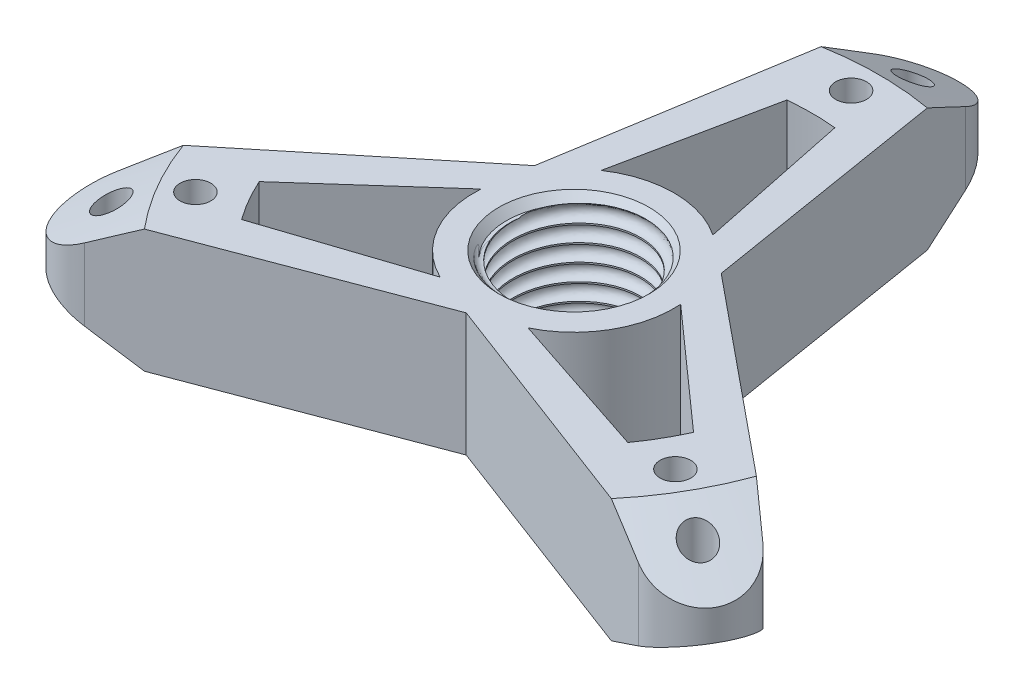
SolidWorks part; units mm, degrees
ref_plane "Front Plane" through (0, 0, 0) normal (0, 0, 1) x (1, 0, 0)
ref_plane "Top Plane" through (0, 0, 0) normal (0, 1, 0) x (1, 0, 0)
ref_plane "Right Plane" through (0, 0, 0) normal (1, 0, 0) x (0, 0, -1)
sketch "Sketch1" plane through (0, 0, 0) normal (0, 1, 0) x (1, 0, 0)
  line L26 (0, 0) -> (0, 22) construction
  line L27 (0, 0) -> (0, 22) construction
  line L36 (0, 0) -> (-6.0622, 3.5) construction
  line L37 (-2.9607, 22.4837) -> (-6.0622, 3.5)
  line L38 (-20.9518, -8.6778) -> (-6.0622, 3.5)
  line L39 (20.9518, -8.6778) -> (6.0622, 3.5)
  line L40 (2.9607, 22.4837) -> (6.0622, 3.5)
  line L41 (-17.9911, -13.8059) -> (0, -7)
  line L42 (17.9911, -13.8059) -> (0, -7)
  circle A24 centre (0, 22) radius 1
  circle A53 centre (19.0526, -11) radius 1
  circle A54 centre (-19.0526, -11) radius 1
  circle A61 centre (0, 0) radius 4.15
  circle A70 centre (0, 0) radius 22 construction
  arc A71 (-2.6648, 17.8017) -> (-17.2575, -5.1164) centre (0, 0) ccw construction
  arc A84 (2.9607, 22.4837) -> (-2.9607, 22.4837) centre (0, 22) ccw
  circle A85 centre (0, 0) radius 7 construction
  circle A86 centre (0, 0) radius 25 construction
  arc A87 (17.9911, -13.8059) -> (20.9518, -8.6778) centre (19.0526, -11) ccw
  arc A88 (-20.9518, -8.6778) -> (-17.9911, -13.8059) centre (-19.0526, -11) ccw
  circle A89 centre (0, 18) radius 1
  circle A90 centre (15.5885, -9) radius 1
  circle A91 centre (-15.5885, -9) radius 1
  point P21 (0, 0)
  point P31 (0, 0)
  point P33 (0, 0)
  point P37 (0, 0)
  point P47 (0, 0)
  point P48 (0, 0)
  point P66 (0, 0)
  dimension "D1" = 8.3
  dimension "D2" = 14
  dimension "D3" = 44
  dimension "D4" = 3
  dimension "D5" = 50
  dimension "D6" = 2
  dimension "D8" = 3
  dimension "D9" = 2
  dimension "D10" = 4
  dimension "D7" = 60
extrude "Boss-Extrude1" add sketch "Sketch1" against normal mid plane 8 contours A86 A24 A53 A54 A85 | A85 L40 A84 L37 A24 | L42 A87 L39 A85 A53 region at (0, 0, -24.4113)
ref_plane "Plane4" through (0, -5, 0) normal (0, 1, 0) x (1, 0, 0)
sketch "Sketch54" plane through (0, -5, 0) normal (0, 1, 0) x (1, 0, 0)
  circle A0 centre (0, 0) radius 4.15 construction
  circle A1 centre (0, 0) radius 4.15
curve "Helix/Spiral2" pitch 1.1 height 16.5 radius 4.15 left hand yes centre (0, -5, 0) axis (0, 1, 0) start towards (0, 0, 1)
sweep "Cut-Sweep4" cut path "Helix/Spiral2" align with end faces yes circular profile diameter 1 parameters "D3"=1
sketch "Sketch62" plane through (0, 4, 0) normal (0, 1, 0) x (1, 0, 0)
  circle A0 centre (0, 0) radius 4.8812
extrude "Cut-Extrude4" cut sketch "Sketch62" against normal blind 0.5 draft 45
mirror "Mirror6" about plane through (0, 0, 0) normal (0, 1, 0) of "Cut-Extrude4"
sketch "Sketch73" plane through (0, 0, 0) normal (1, 0, 0) x (0, 0, -1)
  line L0 (-14, -1) -> (-8.8038, -4)
  line L1 (-14, 4) -> (-14, -4) construction
  line L2 (-8.6778, -4) -> (3.5, -4) construction
  line L3 (-8.8038, -4) -> (-14, -8.8856)
  line L4 (-14, -8.8856) -> (-14, -1)
  line L5 (-14, -4) -> (-8.6778, -4) construction
  line L6 (0, 0) -> (0, -12.6592) construction
  dimension "D1" = 60
  dimension "D2" = 3
sketch "Sketch74" plane through (0, 0, 0) normal (1, 0, 0) x (0, 0, -1)
  line L0 (25, 1) -> (19.8038, 4)
  line L1 (25, -4) -> (25, 4) construction
  line L2 (22.4837, 4) -> (3.5, 4) construction
  line L3 (19.8038, 4) -> (25, 4)
  line L4 (25, 4) -> (22.4837, 4) construction
  line L5 (25, 4) -> (25, 1)
  dimension "D1" = 3
  dimension "D2" = 60
revolve "Cut-Revolve1" cut sketch "Sketch74" angle 360 about L6
mirror "Mirror8" about plane through (0, 0, 0) normal (0, 1, 0) of "Cut-Revolve1"
sketch "Sketch75" plane through (0, 4, 0) normal (0, 1, 0) x (1, 0, 0)
  line L4 (1.5619, 15.3855) -> (3.6284, 5.3931)
  line L5 (-1.5619, 15.3855) -> (-3.6284, 5.3931)
  arc A0 (3.6284, 5.3931) -> (-3.6284, 5.3931) centre (0, 0) ccw
  arc A2 (1.5619, 15.3855) -> (-1.5619, 15.3855) centre (0, 0) ccw
extrude "Cut-Extrude8" cut sketch "Sketch75" against normal blind 16
pattern_circular "CirPattern1" count 3 over 360 about axis through (0, 4, 0) along (0, 1, 0) of "Cut-Extrude8"
sketch "Sketch76" plane through (0, -4, 0) normal (0, -1, 0) x (1, 0, 0)
  circle A0 centre (0, 0) radius 4.8812
  circle A1 centre (0, 0) radius 3
  dimension "D1" = 6
extrude "Boss-Extrude2" add sketch "Sketch76" against normal blind 1
